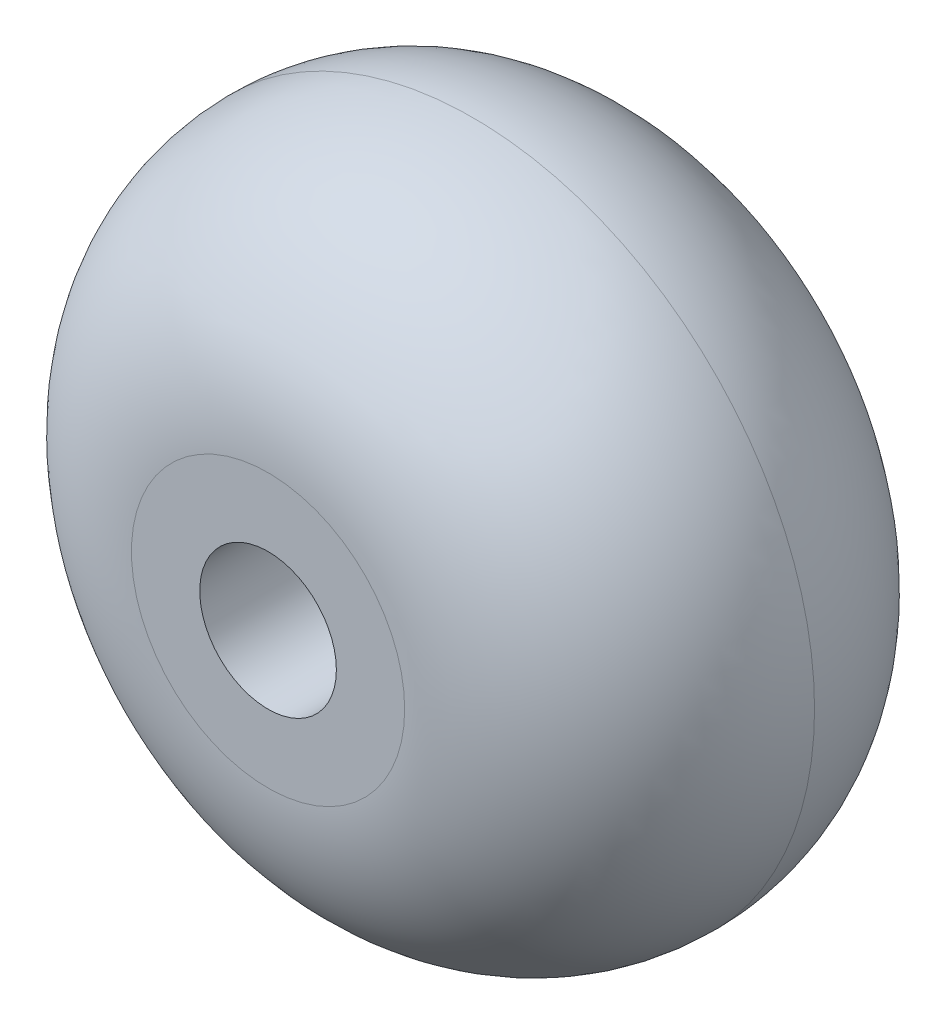
SolidWorks part; units mm, degrees
ref_plane "Płaszczyzna przednia" through (0, 0, 0) normal (0, 0, 1) x (1, 0, 0)
ref_plane "Płaszczyzna górna" through (0, 0, 0) normal (0, 1, 0) x (1, 0, 0)
ref_plane "Płaszczyzna prawa" through (0, 0, 0) normal (1, 0, 0) x (0, 0, -1)
sketch "Szkic1" plane through (0, 0, 0) normal (0, 0, 1) x (1, 0, 0)
  circle A0 centre (0, 0) radius 25
extrude "Dodanie-wyciągnięcie1" add sketch "Szkic1" along normal blind 30
sketch "Szkic2" plane through (0, 0, 30) normal (0, 0, 1) x (1, 0, 0)
  circle A0 centre (0, 0) radius 5
extrude "Wytnij-wyciągnięcie1" cut sketch "Szkic2" against normal blind 30
fillet "Zaokrąglenie1" radius 15 2 edges at (25, 0, 0) (25, 0, 30)
